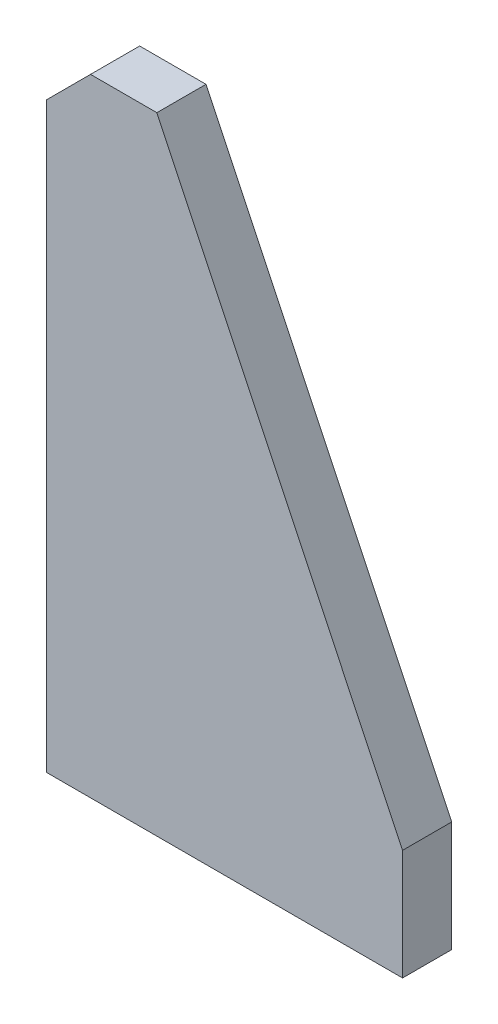
SolidWorks part; units mm, degrees
ref_plane "Спереди" through (0, 0, 0) normal (0, 0, 1) x (1, 0, 0)
ref_plane "Сверху" through (0, 0, 0) normal (0, 1, 0) x (1, 0, 0)
ref_plane "Справа" through (0, 0, 0) normal (1, 0, 0) x (0, 0, -1)
sketch "Эскиз1" plane through (0, 0, 0) normal (0, 0, 1) x (1, 0, 0)
  line L0 (0, 0) -> (0, 45)
  line L1 (0, 45) -> (-100, 255)
  line L2 (-100, 255) -> (-127, 255)
  line L3 (-145, 237) -> (-145, 0)
  line L4 (-145, 0) -> (0, 0)
  line L5 (-127, 255) -> (-145, 237)
extrude "Бобышка-Вытянуть1" add sketch "Эскиз1" along normal blind 20 contours L3 L4 L0 L1 L2 L5
